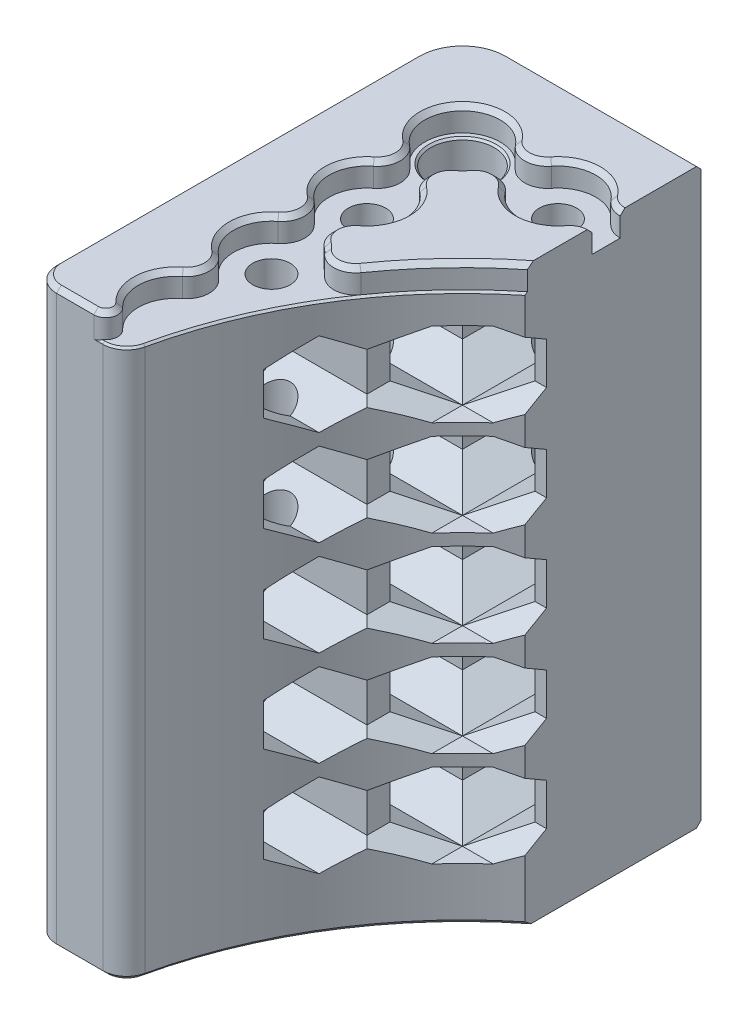
SolidWorks part; units mm, degrees
material "PET"
ref_plane "Front Plane" through (0, 0, 0) normal (0, 0, 1) x (1, 0, 0)
ref_plane "Top Plane" through (0, 0, 0) normal (0, 1, 0) x (1, 0, 0)
ref_plane "Right Plane" through (0, 0, 0) normal (1, 0, 0) x (0, 0, -1)
sketch "Sketch2" plane through (0, 0, 0) normal (0, 1, 0) x (1, 0, 0)
  line L0 (0, 0) -> (0, -53.975)
  line L1 (0, 0) -> (53.975, 0)
  line L2 (57.15, -3.175) -> (57.15, -11.935)
  line L3 (3.175, -57.15) -> (9.3269, -57.15)
  circle A0 centre (66.675, -66.675) radius 55.5625
  circle A1 centre (53.975, -3.175) radius 3.175
  circle A2 centre (53.975, -9.3269) radius 3.175
  circle A3 centre (3.175, -53.975) radius 3.175
  circle A4 centre (9.3269, -53.975) radius 3.175
  circle A5 centre (6.35, -6.35) radius 6.35
  dimension "D2" = 111.125
  dimension "D3" = 6.35
  dimension "D6" = 6.35
  dimension "D7" = 12.7
  dimension "D1" = 53.975
  dimension "D4" = 66.675
  dimension "D5" = 66.675
extrude "Boss-Extrude1" add sketch "Sketch2" along normal blind 76.2 contours A4 A0 A2 A1 L1 L0 A3 | A4 A3 | A4 A3 L3 | A4 A3 | A2 A1 | A2 L2 A1 | A2 A1 | A3 A4 | A1 A2 | A5 region at (20.4992, 0, 20.4992) region at (6.35, 0, 6.35) region at (3.1546, 0, 53.975) region at (53.975, 0, 3.1546) region at (6.251, 0, 56.5266) region at (9.3473, 0, 53.975) region at (6.251, 0, 53.975) region at (56.5266, 0, 6.251) region at (53.975, 0, 6.251) region at (53.975, 0, 9.3473)
sketch "Sketch3" plane through (0, 0, 0) normal (-1, 0, 0) x (0, 0, 1)
  line L0 (6.35, 0) -> (53.975, 0) construction
  line L2 (0, 76.2) -> (0, 0) construction
  circle A0 centre (25.4, 12.7) radius 2.4892
  circle A1 centre (38.1, 12.7) radius 2.4892
  circle A2 centre (38.1, 25.4) radius 2.4892
  circle A3 centre (38.1, 38.1) radius 2.4892
  circle A4 centre (38.1, 50.8) radius 2.4892
  circle A5 centre (38.1, 63.5) radius 2.4892
  circle A6 centre (25.4, 25.4) radius 2.4892
  circle A7 centre (25.4, 38.1) radius 2.4892
  circle A8 centre (25.4, 50.8) radius 2.4892
  circle A9 centre (25.4, 63.5) radius 2.4892
  dimension "D1" = 4.9784
  dimension "D2" = 12.7
  dimension "D3" = 25.4
  dimension "D6" = 12.7
  dimension "D7" = 12.7
  dimension "D4" = 2
  dimension "D5" = 5
extrude "Cut-Extrude1" cut sketch "Sketch3" against normal blind 76.2
sketch "Sketch4" plane through (0, 0, 0) normal (0, 0, -1) x (-1, 0, 0)
  line L0 (-6.35, 0) -> (-53.975, 0) construction
  line L1 (-6.35, 76.2) -> (-6.35, 0) construction
  circle A0 centre (-25.4, 12.7) radius 2.4892
  circle A1 centre (-38.1, 12.7) radius 2.4892
  circle A2 centre (-38.1, 25.4) radius 2.4892
  circle A3 centre (-38.1, 38.1) radius 2.4892
  circle A4 centre (-38.1, 50.8) radius 2.4892
  circle A5 centre (-38.1, 63.5) radius 2.4892
  circle A6 centre (-25.4, 25.4) radius 2.4892
  circle A7 centre (-25.4, 38.1) radius 2.4892
  circle A8 centre (-25.4, 50.8) radius 2.4892
  circle A9 centre (-25.4, 63.5) radius 2.4892
  dimension "D1" = 4.9784
  dimension "D2" = 12.7
  dimension "D3" = 19.05
  dimension "D6" = 12.7
  dimension "D7" = 12.7
  dimension "D4" = 2
  dimension "D5" = 5
extrude "Cut-Extrude2" cut sketch "Sketch4" against normal blind 76.2
sketch "Sketch5" plane through (0, 76.2, 0) normal (0, 1, 0) x (1, 0, 0)
  line L0 (12.7, -12.7) -> (12.7, -25.4) construction
  line L1 (12.7, -25.4) -> (12.7, -38.1) construction
  line L2 (12.7, -12.7) -> (25.4, -12.7) construction
  line L3 (25.4, -12.7) -> (38.1, -12.7) construction
  line L4 (0, -6.35) -> (0, -53.975) construction
  line L5 (6.35, 0) -> (53.975, 0) construction
  circle A0 centre (12.7, -12.7) radius 4.2228
  circle A1 centre (25.4, -12.7) radius 2.4892
  circle A2 centre (38.1, -12.7) radius 2.4892
  circle A3 centre (12.7, -25.4) radius 2.4892
  circle A4 centre (12.7, -38.1) radius 2.4892
  point P10 (8.7437, -31.4549)
  point P12 (8.7217, -31.8126)
  point P16 (32.556, -12.7)
  point P17 (27.2703, -12.7)
  dimension "D1" = 8.4455
  dimension "D2" = 4.9784
  dimension "D3" = 12.7
  dimension "D4" = 12.7
  dimension "D5" = 12.7
  dimension "D6" = 12.7
  dimension "D7" = 12.7
extrude "Cut-Extrude3" cut sketch "Sketch5" against normal through all contours A0 region at (12.7, 76.2, 12.7)
sketch "Sketch8" plane through (0, 76.2, 0) normal (0, 1, 0) x (1, 0, 0)
  circle A0 centre (12.7, -38.1) radius 2.4892 construction
  circle A1 centre (12.7, -25.4) radius 2.4892 construction
  circle A2 centre (38.1, -12.7) radius 2.4892 construction
  circle A3 centre (25.4, -12.7) radius 2.4892 construction
  circle A4 centre (12.7, -38.1) radius 2.4892
  circle A5 centre (12.7, -25.4) radius 2.4892
  circle A6 centre (38.1, -12.7) radius 2.4892
  circle A7 centre (25.4, -12.7) radius 2.4892
extrude "Cut-Extrude5" cut sketch "Sketch8" against normal blind 35.56
sketch "Sketch7" plane through (0, 76.2, 0) normal (0, 1, 0) x (1, 0, 0)
  line L0 (3.175, -57.15) -> (9.3269, -57.15) construction
  line L1 (6.35, 0) -> (53.975, 0) construction
  line L2 (57.15, -3.175) -> (57.15, -9.3269) construction
  line L3 (0, -6.35) -> (0, -53.975) construction
  line L4 (6.35, 0) -> (53.975, 0)
  line L5 (57.15, -3.175) -> (57.15, -9.3269)
  line L6 (3.175, -57.15) -> (9.3269, -57.15)
  line L7 (0, -6.35) -> (0, -53.975)
  circle A0 centre (12.7, -12.7) radius 5.0165
  circle A1 centre (25.4, -12.7) radius 5.0165
  circle A2 centre (38.1, -12.7) radius 5.0165
  circle A3 centre (12.7, -25.4) radius 5.0165
  circle A4 centre (12.7, -38.1) radius 5.0165
  arc A5 (9.6076, -21.45) -> (9.6076, -16.65) centre (7.7287, -19.05) ccw
  arc A6 (9.6076, -34.15) -> (9.6076, -29.35) centre (7.7287, -31.75) ccw
  arc A7 (29.35, -9.6076) -> (34.15, -9.6076) centre (31.75, -7.7287) ccw
  arc A8 (16.65, -9.6076) -> (21.45, -9.6076) centre (19.05, -7.7287) ccw
  arc A9 (9.6076, -46.85) -> (9.6076, -42.05) centre (7.7287, -44.45) ccw
  arc A10 (8.1249, -57.15) -> (9.2247, -54.4177) centre (8.1249, -55.5625) ccw
  arc A11 (9.6076, -46.85) -> (9.2247, -54.4177) centre (12.7, -50.8) ccw
  arc A12 (57.15, -3.175) -> (53.975, 0) centre (53.975, -3.175) ccw construction
  arc A13 (6.35, 0) -> (0, -6.35) centre (6.35, -6.35) ccw construction
  circle A14 centre (12.7, -25.4) radius 2.4892 construction
  arc A15 (9.3269, -57.15) -> (12.4268, -54.6615) centre (9.3269, -53.975) ccw construction
  arc A16 (54.6615, -12.4268) -> (12.4268, -54.6615) centre (66.675, -66.675) ccw construction
  arc A17 (0, -53.975) -> (3.175, -57.15) centre (3.175, -53.975) ccw construction
  arc A18 (57.15, -3.175) -> (53.975, 0) centre (53.975, -3.175) ccw
  arc A19 (6.35, 0) -> (0, -6.35) centre (6.35, -6.35) ccw
  arc A20 (54.6615, -12.4268) -> (57.15, -9.3269) centre (53.975, -9.3269) ccw
  arc A21 (9.3269, -57.15) -> (12.4268, -54.6615) centre (9.3269, -53.975) ccw
  arc A22 (54.6615, -12.4268) -> (12.4268, -54.6615) centre (66.675, -66.675) ccw
  arc A23 (0, -53.975) -> (3.175, -57.15) centre (3.175, -53.975) ccw
  arc A24 (54.4177, -9.2247) -> (46.85, -9.6076) centre (50.8, -12.7) ccw
  arc A25 (54.4177, -9.2247) -> (57.15, -8.1249) centre (55.5625, -8.1249) ccw
  arc A26 (42.05, -9.6076) -> (46.85, -9.6076) centre (44.45, -7.7287) ccw
  arc A27 (55.7937, -11.9294) -> (11.9294, -55.7937) centre (66.675, -66.675) ccw
  arc A28 (34.5329, -21.0421) -> (34.7825, -16.4629) centre (32.8508, -18.654) ccw
  arc A29 (16.4629, -34.7825) -> (21.0421, -34.5329) centre (18.654, -32.8508) ccw
  arc A30 (34.0868, -15.7099) -> (29.4132, -15.7099) centre (31.75, -17.4625) ccw
  arc A31 (15.7099, -29.4132) -> (15.7099, -34.0868) centre (17.4625, -31.75) ccw
  arc A32 (15.7099, -16.7132) -> (15.7099, -21.3868) centre (17.4625, -19.05) ccw
  arc A33 (21.3868, -15.7099) -> (16.7132, -15.7099) centre (19.05, -17.4625) ccw
  circle A34 centre (12.7, -38.1) radius 2.4892 construction
  circle A38 centre (38.1, -12.7) radius 2.4892 construction
  circle A39 centre (25.4, -12.7) radius 2.4892 construction
  arc A40 (54.6615, -12.4268) -> (57.15, -9.3269) centre (53.975, -9.3269) ccw construction
  point P72 (25.4709, -12.7)
  point P78 (38.504, -13.1204)
  point P79 (0, 0)
  point P81 (0, 0)
  point P82 (20.6375, -13.4232)
  point P83 (21.0421, -6.5038)
  point P84 (20.3774, -17.8539)
  point P85 (21.3868, -15.7099)
  point P86 (16.7132, -15.7099)
  point P92 (13.5772, -25.8367)
  point P95 (0, 0)
  circle M5 centre (12.7, -12.7) radius 4.2228
  arc M6 (54.6615, -12.4268) -> (57.15, -9.3269) centre (53.975, -9.3269) ccw
  line M7 (57.15, -9.3269) -> (57.15, -3.175)
  arc M14 (9.3269, -57.15) -> (12.4268, -54.6615) centre (9.3269, -53.975) ccw
  arc M15 (12.4268, -54.6615) -> (54.6615, -12.4268) centre (66.675, -66.675) cw
  circle M59 centre (12.7, -38.1) radius 2.4892
  circle M60 centre (25.4, -12.7) radius 2.4892
  circle M61 centre (38.1, -12.7) radius 2.4892
  circle M62 centre (12.7, -25.4) radius 2.4892
  dimension "D1" = 10.033
  dimension "D2" = 6.096
  dimension "D3" = 3.175
  dimension "D4" = 111.633
  dimension "D5" = 5.842
extrude "Cut-Extrude8" cut sketch "Sketch7" against normal blind 3.175 contours A0 M5 | A32 A0 A5 A3 | A3 M62 | A31 A3 A6 A4 | A4 M59 | A29 A4 A9 A11 A10 L6 A27 M14 | A27 A21 M6 M15 | A33 A1 A8 A0 | A1 M60 | A30 A2 A7 A1 | A28 A27 A20 A25 A24 A26 A2 M7 | A2 M61 region at (47.9531, 76.2, 12.1291) region at (12.1291, 76.2, 47.9531) region at (55.2271, 76.2, 12.177) region at (42.7083, 76.2, 11.1107) region at (31.75, 76.2, 12.6504) region at (7.8254, 76.2, 38.1) region at (30.0083, 76.2, 11.1107) region at (12.6504, 76.2, 31.75) region at (19.05, 76.2, 12.6504) region at (7.8254, 76.2, 25.4) region at (17.3083, 76.2, 11.1107) region at (12.6504, 76.2, 19.05)
ref_plane "Plane1" through (57.15, 0, 0) normal (1, 0, 0) x (0, 0, -1)
ref_plane "Plane2" through (0, 0, 57.15) normal (0, 0, 1) x (1, 0, 0)
sketch "Sketch9" plane through (57.15, 0, 0) normal (1, 0, 0) x (0, 0, -1)
  line L1 (-42.926, 66.2863) -> (-42.926, 60.7137)
  line L2 (-42.926, 60.7137) -> (-38.1, 57.9274)
  line L3 (-38.1, 57.9274) -> (-33.274, 60.7137)
  line L4 (-33.274, 60.7137) -> (-33.274, 66.2863)
  line L5 (-33.274, 66.2863) -> (-38.1, 69.0726)
  line L6 (-38.1, 69.0726) -> (-42.926, 66.2863)
  line L7 (-20.574, 66.2863) -> (-25.4, 69.0726)
  line L8 (-25.4, 69.0726) -> (-30.226, 66.2863)
  line L9 (-30.226, 66.2863) -> (-30.226, 60.7137)
  line L10 (-30.226, 60.7137) -> (-25.4, 57.9274)
  line L11 (-25.4, 57.9274) -> (-20.574, 60.7137)
  line L12 (-20.574, 60.7137) -> (-20.574, 66.2863)
  line L13 (-20.574, 53.5863) -> (-25.4, 56.3726)
  line L14 (-25.4, 56.3726) -> (-30.226, 53.5863)
  line L15 (-30.226, 53.5863) -> (-30.226, 48.0137)
  line L16 (-30.226, 48.0137) -> (-25.4, 45.2274)
  line L17 (-25.4, 45.2274) -> (-20.574, 48.0137)
  line L18 (-20.574, 48.0137) -> (-20.574, 53.5863)
  line L19 (-33.274, 53.5863) -> (-38.1, 56.3726)
  line L20 (-38.1, 56.3726) -> (-42.926, 53.5863)
  line L21 (-42.926, 53.5863) -> (-42.926, 48.0137)
  line L22 (-42.926, 48.0137) -> (-38.1, 45.2274)
  line L23 (-38.1, 45.2274) -> (-33.274, 48.0137)
  line L24 (-33.274, 48.0137) -> (-33.274, 53.5863)
  line L25 (-38.1, 43.6726) -> (-42.926, 40.8863)
  line L26 (-42.926, 40.8863) -> (-42.926, 35.3137)
  line L27 (-42.926, 35.3137) -> (-38.1, 32.5274)
  line L28 (-38.1, 32.5274) -> (-33.274, 35.3137)
  line L29 (-33.274, 35.3137) -> (-33.274, 40.8863)
  line L30 (-33.274, 40.8863) -> (-38.1, 43.6726)
  line L31 (-20.574, 40.8863) -> (-25.4, 43.6726)
  line L32 (-25.4, 43.6726) -> (-30.226, 40.8863)
  line L33 (-30.226, 40.8863) -> (-30.226, 35.3137)
  line L34 (-30.226, 35.3137) -> (-25.4, 32.5274)
  line L35 (-25.4, 32.5274) -> (-20.574, 35.3137)
  line L36 (-20.574, 35.3137) -> (-20.574, 40.8863)
  line L37 (-20.574, 28.1863) -> (-25.4, 30.9726)
  line L38 (-25.4, 30.9726) -> (-30.226, 28.1863)
  line L39 (-30.226, 28.1863) -> (-30.226, 22.6137)
  line L40 (-30.226, 22.6137) -> (-25.4, 19.8274)
  line L41 (-25.4, 19.8274) -> (-20.574, 22.6137)
  line L42 (-20.574, 22.6137) -> (-20.574, 28.1863)
  line L43 (-33.274, 28.1863) -> (-38.1, 30.9726)
  line L44 (-38.1, 30.9726) -> (-42.926, 28.1863)
  line L45 (-42.926, 28.1863) -> (-42.926, 22.6137)
  line L46 (-42.926, 22.6137) -> (-38.1, 19.8274)
  line L47 (-38.1, 19.8274) -> (-33.274, 22.6137)
  line L48 (-33.274, 22.6137) -> (-33.274, 28.1863)
  line L49 (-38.1, 18.2726) -> (-42.926, 15.4863)
  line L50 (-42.926, 15.4863) -> (-42.926, 9.9137)
  line L51 (-42.926, 9.9137) -> (-38.1, 7.1274)
  line L52 (-38.1, 7.1274) -> (-33.274, 9.9137)
  line L53 (-33.274, 9.9137) -> (-33.274, 15.4863)
  line L54 (-33.274, 15.4863) -> (-38.1, 18.2726)
  line L55 (-20.574, 15.4863) -> (-25.4, 18.2726)
  line L56 (-25.4, 18.2726) -> (-30.226, 15.4863)
  line L57 (-30.226, 15.4863) -> (-30.226, 9.9137)
  line L58 (-30.226, 9.9137) -> (-25.4, 7.1274)
  line L59 (-25.4, 7.1274) -> (-20.574, 9.9137)
  line L60 (-20.574, 9.9137) -> (-20.574, 15.4863)
  circle A0 centre (-38.1, 63.5) radius 4.826 construction
  circle A1 centre (-25.4, 63.5) radius 4.826 construction
  circle A2 centre (-25.4, 50.8) radius 4.826 construction
  circle A3 centre (-38.1, 50.8) radius 4.826 construction
  circle A4 centre (-38.1, 38.1) radius 4.826 construction
  circle A5 centre (-25.4, 38.1) radius 4.826 construction
  circle A6 centre (-25.4, 25.4) radius 4.826 construction
  circle A7 centre (-38.1, 25.4) radius 4.826 construction
  circle A8 centre (-38.1, 12.7) radius 4.826 construction
  circle A9 centre (-25.4, 12.7) radius 4.826 construction
  point P82 (-40.9125, 13.2243)
  point P91 (-33.274, 38.1)
  point P92 (0, 0)
  point P93 (-41.275, 69.0726)
  dimension "D1" = 9.652
extrude "Cut-Extrude6" cut sketch "Sketch9" against normal offset from surface (47.625 mm away) 9.525 up to face at (0, 63.5, 40.5892)
chamfer "Chamfer3" distance 0.254 angle 45 6 edges at (12.7, 73.025, 16.9228) (57.15, 73.025, 8.7259) (56.4509, 73.025, 11.3145) (8.7259, 73.025, 57.15) (27.3864, 73.025, 27.3864) (11.3145, 73.025, 56.4509)
chamfer "Chamfer4" distance 0.635 angle 45 40 edges at (31.75, 76.2, 14.5415) (35.7675, 76.2, 18.813) (19.05, 76.2, 14.5415) (27.2068, 76.2, 27.2068) (18.813, 76.2, 35.7675) (14.5415, 76.2, 31.75) (14.5415, 76.2, 19.05) (10.7767, 76.2, 19.05) (9.1528, 76.2, 9.1528) (19.05, 76.2, 10.7767) (25.4, 76.2, 7.6835) (31.75, 76.2, 10.7767) (38.1, 76.2, 7.6835) (44.45, 76.2, 10.7767) (50.5465, 76.2, 7.6899) (56.1553, 76.2, 9.5976) (57.15, 76.2, 5.65) (56.2201, 76.2, 0.9299) (30.1625, 76.2, 0) (1.8599, 76.2, 1.8599) (0, 76.2, 30.1625) (0.9299, 76.2, 56.2201) (5.65, 76.2, 57.15) (9.5976, 76.2, 56.1553) (7.6899, 76.2, 50.5465) (10.7767, 76.2, 44.45) (7.6835, 76.2, 38.1) (10.7767, 76.2, 31.75) (7.6835, 76.2, 25.4) (12.7, 0, 16.9228) (56.2201, 0, 0.9299) (57.15, 0, 6.251) (56.4509, 0, 11.3145) (30.1625, 0, 0) (1.8599, 0, 1.8599) (0, 0, 30.1625) (0.9299, 0, 56.2201) (6.251, 0, 57.15) (27.3864, 0, 27.3864) (11.3145, 0, 56.4509)
sketch "Sketch13" plane through (0, 0, 57.15) normal (0, 0, 1) x (1, 0, 0)
  line L1 (25.4, 69.0726) -> (20.574, 66.2863)
  line L2 (20.574, 66.2863) -> (20.574, 60.7137)
  line L3 (20.574, 60.7137) -> (25.4, 57.9274)
  line L4 (25.4, 57.9274) -> (30.226, 60.7137)
  line L5 (30.226, 60.7137) -> (30.226, 66.2863)
  line L6 (30.226, 66.2863) -> (25.4, 69.0726)
  line L7 (42.926, 66.2863) -> (38.1, 69.0726)
  line L8 (38.1, 69.0726) -> (33.274, 66.2863)
  line L9 (33.274, 66.2863) -> (33.274, 60.7137)
  line L10 (33.274, 60.7137) -> (38.1, 57.9274)
  line L11 (38.1, 57.9274) -> (42.926, 60.7137)
  line L12 (42.926, 60.7137) -> (42.926, 66.2863)
  line L13 (42.926, 53.5863) -> (38.1, 56.3726)
  line L14 (38.1, 56.3726) -> (33.274, 53.5863)
  line L15 (33.274, 53.5863) -> (33.274, 48.0137)
  line L16 (33.274, 48.0137) -> (38.1, 45.2274)
  line L17 (38.1, 45.2274) -> (42.926, 48.0137)
  line L18 (42.926, 48.0137) -> (42.926, 53.5863)
  line L19 (30.226, 53.5863) -> (25.4, 56.3726)
  line L20 (25.4, 56.3726) -> (20.574, 53.5863)
  line L21 (20.574, 53.5863) -> (20.574, 48.0137)
  line L22 (20.574, 48.0137) -> (25.4, 45.2274)
  line L23 (25.4, 45.2274) -> (30.226, 48.0137)
  line L24 (30.226, 48.0137) -> (30.226, 53.5863)
  line L25 (30.226, 40.8863) -> (25.4, 43.6726)
  line L26 (25.4, 43.6726) -> (20.574, 40.8863)
  line L27 (20.574, 40.8863) -> (20.574, 35.3137)
  line L28 (20.574, 35.3137) -> (25.4, 32.5274)
  line L29 (25.4, 32.5274) -> (30.226, 35.3137)
  line L30 (30.226, 35.3137) -> (30.226, 40.8863)
  line L31 (42.926, 40.8863) -> (38.1, 43.6726)
  line L32 (38.1, 43.6726) -> (33.274, 40.8863)
  line L33 (33.274, 40.8863) -> (33.274, 35.3137)
  line L34 (33.274, 35.3137) -> (38.1, 32.5274)
  line L35 (38.1, 32.5274) -> (42.926, 35.3137)
  line L36 (42.926, 35.3137) -> (42.926, 40.8863)
  line L37 (42.926, 28.1863) -> (38.1, 30.9726)
  line L38 (38.1, 30.9726) -> (33.274, 28.1863)
  line L39 (33.274, 28.1863) -> (33.274, 22.6137)
  line L40 (33.274, 22.6137) -> (38.1, 19.8274)
  line L41 (38.1, 19.8274) -> (42.926, 22.6137)
  line L42 (42.926, 22.6137) -> (42.926, 28.1863)
  line L43 (30.226, 28.1863) -> (25.4, 30.9726)
  line L44 (25.4, 30.9726) -> (20.574, 28.1863)
  line L45 (20.574, 28.1863) -> (20.574, 22.6137)
  line L46 (20.574, 22.6137) -> (25.4, 19.8274)
  line L47 (25.4, 19.8274) -> (30.226, 22.6137)
  line L48 (30.226, 22.6137) -> (30.226, 28.1863)
  line L49 (30.226, 15.4863) -> (25.4, 18.2726)
  line L50 (25.4, 18.2726) -> (20.574, 15.4863)
  line L51 (20.574, 15.4863) -> (20.574, 9.9137)
  line L52 (20.574, 9.9137) -> (25.4, 7.1274)
  line L53 (25.4, 7.1274) -> (30.226, 9.9137)
  line L54 (30.226, 9.9137) -> (30.226, 15.4863)
  line L55 (42.926, 15.4863) -> (38.1, 18.2726)
  line L56 (38.1, 18.2726) -> (33.274, 15.4863)
  line L57 (33.274, 15.4863) -> (33.274, 9.9137)
  line L58 (33.274, 9.9137) -> (38.1, 7.1274)
  line L59 (38.1, 7.1274) -> (42.926, 9.9137)
  line L60 (42.926, 9.9137) -> (42.926, 15.4863)
  circle A0 centre (25.4, 63.5) radius 4.826 construction
  circle A1 centre (38.1, 63.5) radius 4.826 construction
  circle A2 centre (38.1, 50.8) radius 4.826 construction
  circle A3 centre (25.4, 50.8) radius 4.826 construction
  circle A4 centre (25.4, 38.1) radius 4.826 construction
  circle A5 centre (38.1, 38.1) radius 4.826 construction
  circle A6 centre (38.1, 25.4) radius 4.826 construction
  circle A7 centre (25.4, 25.4) radius 4.826 construction
  circle A8 centre (25.4, 12.7) radius 4.826 construction
  circle A9 centre (38.1, 12.7) radius 4.826 construction
  dimension "D1" = 9.652
extrude "Cut-Extrude9" cut sketch "Sketch13" against normal offset from surface (47.625 mm away) 9.525 up to face at (35.6108, 63.5, 0)
sketch "Sketch14" plane through (57.15, 0, 0) normal (1, 0, 0) x (0, 0, -1)
  line L0 (0, 75.565) -> (0, 0.635) construction
  line L1 (-25.4, 69.0726) -> (-29.4787, 69.0726)
  line L2 (-25.4, 69.0726) -> (-25.4, 7.1274)
  line L3 (-25.4, 7.1274) -> (-29.4787, 7.1274)
  line L4 (-29.4787, 69.0726) -> (-29.4787, 7.1274)
  line L5 (-27.3864, 67.9257) -> (-25.4, 69.0726) construction
  line L6 (-25.4, 8.2743) -> (-29.4787, 8.2743)
  line L7 (-29.4787, 17.1257) -> (-25.4, 17.1257)
  line L8 (-29.4787, 20.9743) -> (-25.4, 20.9743)
  line L9 (-29.4787, 45.2274) -> (-25.4, 45.2274)
  line L10 (-29.4787, 29.8257) -> (-25.4, 29.8257)
  line L11 (-25.4, 43.6726) -> (-29.4787, 43.6726)
  line L12 (-29.4787, 33.6743) -> (-25.4, 33.6743)
  line L13 (-29.4787, 32.5274) -> (-25.4, 32.5274)
  line L14 (-29.4787, 46.3743) -> (-25.4, 46.3743)
  line L15 (-29.4787, 42.5257) -> (-25.4, 42.5257)
  line L16 (-29.4787, 55.2257) -> (-25.4, 55.2257)
  line L17 (-29.4787, 59.0743) -> (-25.4, 59.0743)
  line L18 (-29.4787, 67.9257) -> (-25.4, 67.9257)
  line L19 (-25.4, 57.9274) -> (-29.4787, 57.9274)
  line L20 (-29.4787, 56.3726) -> (-25.4, 56.3726)
  line L21 (-25.4, 30.9726) -> (-29.4787, 30.9726)
  line L22 (-29.4787, 19.8274) -> (-25.4, 19.8274)
  line L23 (-25.4, 18.2726) -> (-29.4787, 18.2726)
  dimension "D1" = 25.4
extrude "Cut-Extrude10" cut sketch "Sketch14" against normal up to vertex (31.75 mm away) contours L2 L6 L4 L3 | L2 L23 L4 L7 | L4 L22 L2 L8 | L4 L13 L2 L12 | L2 L21 L4 L10 | L14 L4 L9 L2 | L4 L15 L2 L11 | L19 L2 L17 L4 | L20 L4 L16 L2 | L4 L18 L2 L1 region at (57.15, 68.4992, 27.4393) region at (57.15, 58.5008, 27.4393) region at (57.15, 55.7992, 27.4393) region at (57.15, 45.8008, 27.4393) region at (57.15, 43.0992, 27.4393) region at (57.15, 33.1008, 27.4393) region at (57.15, 30.3992, 27.4393) region at (57.15, 20.4008, 27.4393) region at (57.15, 17.6992, 27.4393) region at (57.15, 7.7008, 27.4393) up to point (25.4, 57.9274, 25.4)
sketch "Sketch15" plane through (0, 0, 0) normal (0, 0, -1) x (-1, 0, 0)
  line L0 (-57.15, 3.3835) -> (-57.15, -3.3835) construction
  line L1 (-31.75, 76.2) -> (-57.15, 76.2)
  line L2 (-31.75, 76.2) -> (-31.75, 0)
  line L3 (-31.75, 0) -> (-57.15, 0)
  line L4 (-57.15, 76.2) -> (-57.15, 0)
  line L5 (-53.975, 76.2) -> (-6.35, 76.2) construction
  line L6 (-6.35, 0) -> (-53.975, 0) construction
  dimension "D1" = 25.4
extrude "Cut-Extrude11" cut sketch "Sketch15" against normal through all
